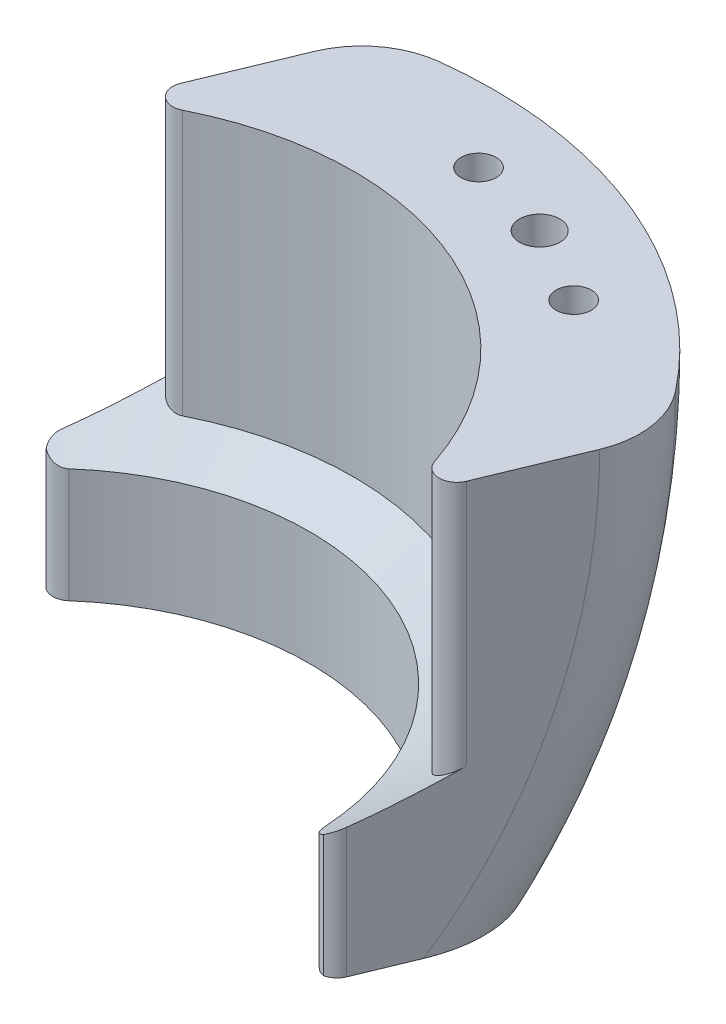
SolidWorks part; units mm, degrees
note: The reader was unsure of these and kept them because the rebuilt part matched: shared geometry of "Эскиз3<3>".
ref_plane "Спереди" through (0, 0, 0) normal (0, 0, 1) x (1, 0, 0)
ref_plane "Сверху" through (0, 0, 0) normal (0, 1, 0) x (1, 0, 0)
ref_plane "Справа" through (0, 0, 0) normal (1, 0, 0) x (0, 0, -1)
sketch "Эскиз1" plane through (0, 0, 0) normal (0, 0, 1) x (1, 0, 0)
  line L0 (0, 0) -> (0, 15) construction
  line L1 (-17.5, 15) -> (17.5, 15) construction
  line L2 (-17.5, 15) -> (-17.5, 0) construction
  line L3 (-17.5, 0) -> (17.5, 0) construction
  line L4 (17.5, 15) -> (17.5, 0)
  line L5 (-17.5, 15) -> (17.5, 0) construction
  line L6 (-17.5, 0) -> (17.5, 15) construction
  line L7 (17.5, 0) -> (15, 0)
  line L8 (15, 0) -> (15, -8)
  line L12 (20, -8) -> (15, -8)
  line L14 (17.5, 15) -> (25.5, 15)
  line L15 (25.5, 15) -> (25.5, -8) construction
  arc A2 (20, -8) -> (25.5, 15) centre (-25.3409, 15) ccw
  point P4 (0, 7.5)
  dimension "D5" = 5
  dimension "D7" = 8
  dimension "D1" = 35
  dimension "D2" = 15
  dimension "D3" = 15
  dimension "D4" = 8
revolve "Повернуть1" add sketch "Эскиз1" angle 135 about L0
sketch "Эскиз2" plane through (0, 15, 0) normal (0, 1, 0) x (1, 0, 0)
  line L0 (-11.6615, 11.0436) -> (16.0549, -0.437)
  line L1 (-11.6615, 11.0436) -> (-4.0998, 29.2992)
  line L2 (16.0549, -0.437) -> (23.6166, 17.8187)
  line L3 (-4.0998, 29.2992) -> (23.6166, 17.8187)
  line L4 (-19.5689, 14.3189) -> (23.9623, -3.7123)
  line L5 (-19.5689, 14.3189) -> (-12.0072, 32.5745)
  line L6 (23.9623, -3.7123) -> (31.524, 14.5433)
  line L7 (-12.0072, 32.5745) -> (31.524, 14.5433)
  arc A0 (25.5, 0) -> (-18.0312, 18.0312) centre (0, 0) ccw construction
  point P0 (9.7584, 23.5589)
  dimension "D1" = 30
extrude "Вырез-Вытянуть1" cut sketch "Эскиз2" against normal through all
sketch "Эскиз3" plane through (0, 15, 0) normal (0, 1, 0) x (1, 0, 0)
  line L2 (6.697, 16.1679) -> (9.7584, 23.5589) construction
  line L3 (-10.4087, 14.068) -> (-5.9667, 24.7921) construction
  line L4 (17.3077, 2.5875) -> (21.7497, 13.3116) construction
  arc A0 (-7.9638, 19.9707) -> (19.7526, 8.4902) centre (0, 0) cw construction
  arc A1 (21.7497, 13.3116) -> (-5.9667, 24.7921) centre (0, 0) ccw construction
  circle A2 centre (3.3827, 21.2322) radius 1
  circle A4 centre (8.2277, 19.8634) radius 1.15
  circle A5 centre (12.6215, 17.4054) radius 1
  arc A6 (17.3077, 2.5875) -> (-10.4087, 14.068) centre (0, 0) ccw construction
  dimension "D1" = 2
  dimension "D2" = 10
  dimension "D4" = 2.3
extrude "Вырез-Вытянуть2" cut sketch "Эскиз3" against normal blind 6 contours A2 | A5
fillet "Скругление1" [suppressed] radius 1
fillet "Скругление2" radius 5 2 edges at (20.9666, 2.2502, -11.4209) (-6.7498, 2.2502, -22.9014)
extrude "Вырез-Вытянуть3" cut sketch "Эскиз3<3>" against normal blind 4 contours A4
sketch "Эскиз3<3>" plane through (0, 15, 0) normal (0, 1, 0) x (1, 0, 0) same geometry as "Эскиз3"
sketch "Эскиз4" plane through (0, 0, 0) normal (0, 1, 0) x (1, 0, 0)
  line L0 (-0.9567, -2.3097) -> (0, 0) construction
  line L1 (-11.4805, 11.4805) -> (-10.4087, 14.068) construction
  circle A0 centre (-0.9567, -2.3097) radius 17.5
  arc A1 (15, 0) -> (-10.6066, 10.6066) centre (0, 0) ccw construction
  point P3 (5.7403, 13.8582)
  dimension "D1" = 35
extrude "Вырез-Вытянуть4" [suppressed] cut sketch "Эскиз4" against normal through all
fillet "Скругление3" [suppressed] radius 1
chamfer "Фаска1" distance 1.5 angle 60 1 edges at (5.7403, 0, -13.8582) first distance on face at (3.9685, -4, -9.5807)
fillet "Скругление4" radius 1 6 edges at (17.3077, 7.4717, -2.5875) (-10.4087, 7.4717, -14.068) (16.2359, -4.3932, 0) (15, -4.75, 0) (-11.4805, -4.3932, -11.4805) (-10.6066, -4.75, -10.6066)
